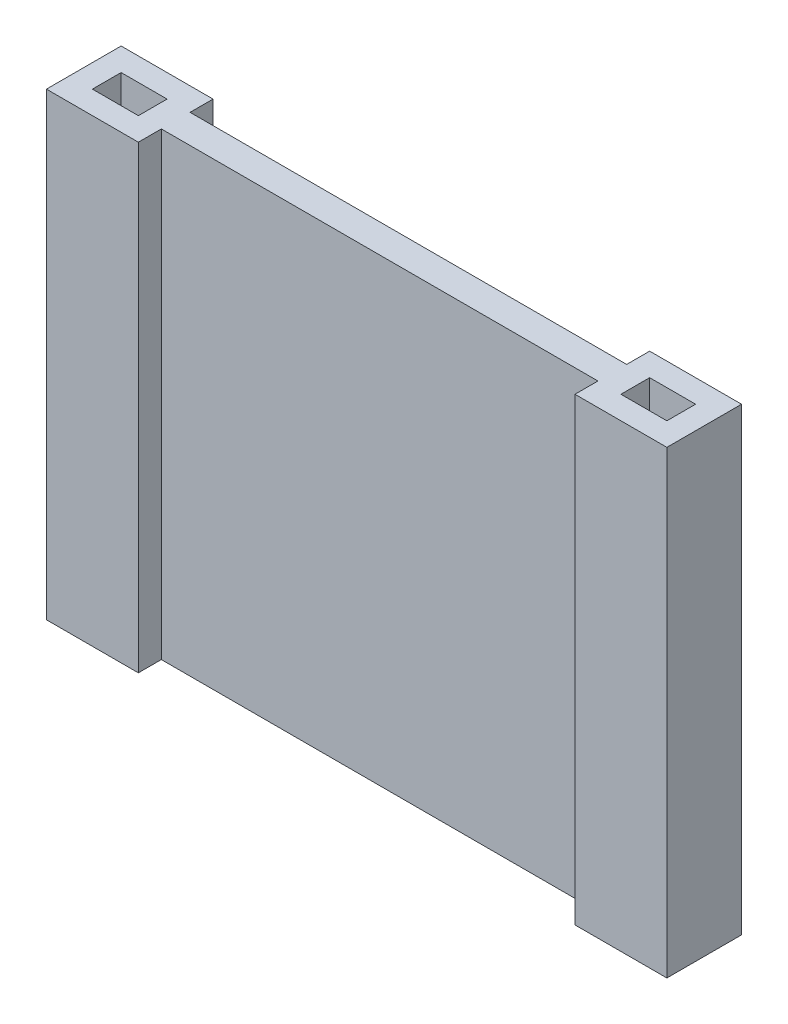
SolidWorks part; units mm, degrees
ref_plane "前视基准面" through (0, 0, 0) normal (0, 0, 1) x (1, 0, 0)
ref_plane "上视基准面" through (0, 0, 0) normal (0, 1, 0) x (1, 0, 0)
ref_plane "右视基准面" through (0, 0, 0) normal (1, 0, 0) x (0, 0, -1)
sketch "草图1" plane through (0, 0, 0) normal (0, 0, 1) x (1, 0, 0)
  line L0 (0, 0) -> (0, -80)
  line L1 (0, -80) -> (80, -80)
  line L2 (80, -80) -> (80, 0)
  line L3 (80, 0) -> (0, 0)
extrude "凸台-拉伸1" add sketch "草图1" along normal blind 5
sketch "草图2" plane through (80, 0, 0) normal (1, 0, 0) x (0, 0, -1)
  line L0 (-5, 0) -> (-9, 0)
  line L1 (0, 0) -> (4, 0)
  line L2 (-9, 0) -> (-9, -80)
  line L3 (-9, -80) -> (-5, -80)
  line L4 (-5, -80) -> (-5, 0)
  line L5 (0, 0) -> (0, -80)
  line L6 (0, -80) -> (4, -80)
  line L7 (4, -80) -> (4, 0)
extrude "凸台-拉伸2" add sketch "草图2" against normal blind 4
extrude "凸台-拉伸3" add sketch "草图2<2>" along normal blind 12
sketch "草图2<2>" plane through (80, 0, 0) normal (1, 0, 0) x (0, 0, -1) same geometry as "草图2"
sketch "草图3" plane through (0, 0, 9) normal (0, 0, 1) x (1, 0, 0)
  line L0 (76, 0) -> (92, 0) construction
  line L1 (92, 0) -> (88, 0)
  line L2 (88, 0) -> (88, -80)
  line L3 (76, -80) -> (92, -80) construction
  line L4 (88, -80) -> (92, -80)
  line L5 (92, -80) -> (92, 0)
extrude "凸台-拉伸4" add sketch "草图3" against normal blind 9
sketch "草图5" plane through (0, 0, 5) normal (0, 0, 1) x (1, 0, 0)
  line L0 (38, 0) -> (38, -80)
  line L1 (76, 0) -> (0, 0) construction
  line L2 (0, -80) -> (76, -80) construction
sketch "草图6" plane through (0, -80, 0) normal (0, -1, 0) x (1, 0, 0)
  line L0 (38, 5) -> (38, 0)
  line L1 (0, 0) -> (76, 0) construction
  line L2 (76, 9) -> (76, -4)
  line L3 (76, -4) -> (92, -4)
  line L4 (92, -4) -> (92, 9)
  line L5 (92, 9) -> (76, 9)
  line L6 (88, 5) -> (80, 5)
  line L7 (80, 5) -> (80, 0)
  line L8 (80, 0) -> (88, 0)
  line L9 (88, 0) -> (88, 5) construction
  line L10 (88, 0) -> (88, 5)
  line L11 (0, -4) -> (-16, -4)
  line L12 (-16, -4) -> (-16, 9)
  line L13 (-12, 0) -> (-12, 5)
  line L14 (-4, 0) -> (-12, 0)
  line L15 (-4, 5) -> (-4, 0)
  line L16 (-12, 5) -> (-4, 5)
  line L17 (0, 9) -> (0, -4)
  line L18 (-16, 9) -> (0, 9)
  line M14 (0, 5) -> (0, 0)
extrude "凸台-拉伸5" add sketch "草图6" against normal blind 80 contours L18 L12 L11 L17 L13 L16 L15 L14 M14 region at (-8, -80, -3.7938)
